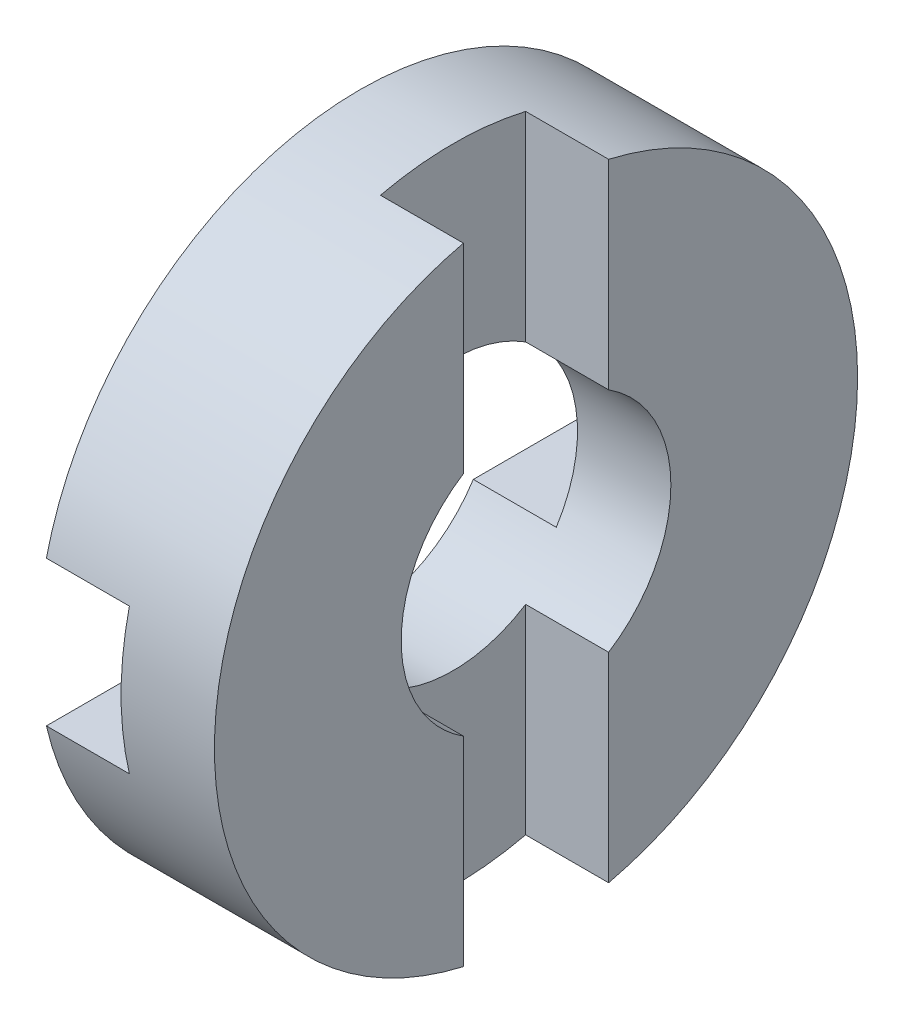
SolidWorks part; units mm, degrees
ref_plane "Front Plane" through (0, 0, 0) normal (0, 0, 1) x (1, 0, 0)
ref_plane "Top Plane" through (0, 0, 0) normal (0, 1, 0) x (1, 0, 0)
ref_plane "Right Plane" through (0, 0, 0) normal (1, 0, 0) x (0, 0, -1)
sketch "Sketch1" plane through (0, 0, 0) normal (0, 0, 1) x (1, 0, 0)
  line L0 (0, 0) -> (8.5, 0) construction
  line L1 (0, 6.5) -> (8.5, 6.5)
  line L2 (0, 6.5) -> (0, 15.5)
  line L3 (0, 15.5) -> (8.5, 15.5)
  line L4 (8.5, 6.5) -> (8.5, 15.5)
  dimension "D3_s" = 13
  dimension "MSM_20" = 8.5
  dimension "D1." = 31
revolve "Revolve1" add sketch "Sketch1" angle 360 about L0
sketch "Sketch2" plane through (0, 0, 0) normal (0, 0, 1) x (1, 0, 0)
  line L1 (0, 3.5) -> (4, 3.5)
  line L2 (0, 3.5) -> (0, -3.5)
  line L3 (0, -3.5) -> (4, -3.5)
  line L4 (4, 3.5) -> (4, -3.5)
  dimension "MSM_21" = 4
  dimension "MSM_22" = 7
extrude "Cut-Extrude1" cut sketch "Sketch2" against normal mid plane 31
sketch "Sketch3" plane through (0, 0, 0) normal (0, 1, 0) x (1, 0, 0)
  line L0 (8.5, -15.5) -> (8.5, 15.5) construction
  line L1 (8.5, -3.5) -> (4.5, -3.5)
  line L2 (8.5, -3.5) -> (8.5, 3.5)
  line L3 (8.5, 3.5) -> (4.5, 3.5)
  line L4 (4.5, -3.5) -> (4.5, 3.5)
  point P4 (8.5, 0)
  dimension "MSM_21" = 4
  dimension "MSM_22" = 7
extrude "Cut-Extrude2" cut sketch "Sketch3" against normal mid plane 31
ref_plane "Plane1" through (4.25, 0, 0) normal (1, 0, 0) x (0, 0, -1)
